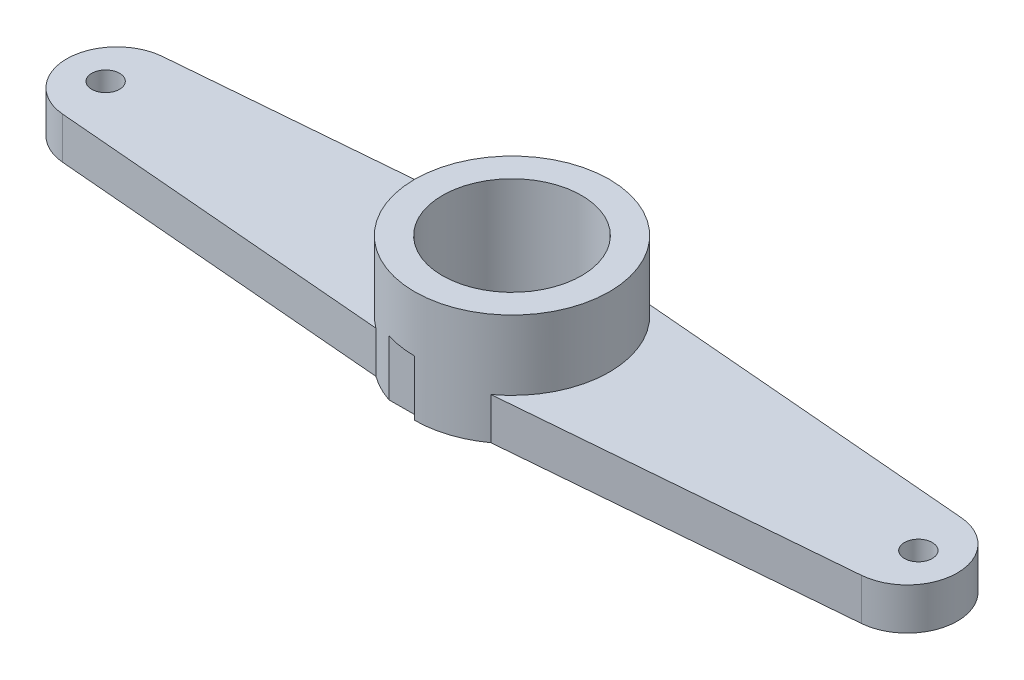
SolidWorks part; units mm, degrees
ref_plane "前视基准面" through (0, 0, 0) normal (0, 0, 1) x (1, 0, 0)
ref_plane "上视基准面" through (0, 0, 0) normal (0, 1, 0) x (1, 0, 0)
ref_plane "右视基准面" through (0, 0, 0) normal (1, 0, 0) x (0, 0, -1)
sketch "草图1" plane through (0, 0, 0) normal (0, 1, 0) x (1, 0, 0)
  line L0 (-14.2, 0) -> (14.2, 0) construction
  line L1 (0, 3) -> (0, -3) construction
  line L2 (14.3508, 1.7937) -> (0, 3)
  line L3 (14.3508, -1.7937) -> (0, -3)
  line L4 (-14.3508, 1.7937) -> (0, 3)
  line L5 (-14.3508, -1.7937) -> (0, -3)
  circle A0 centre (14.2, 0) radius 1.8
  circle A1 centre (-14.2, 0) radius 1.8
  circle A2 centre (0, 0) radius 3.4998
  point P4 (0, 0)
  point P12 (0, 0)
  dimension "D1" = 3.6
  dimension "D2" = 6
extrude "凸台-拉伸1" add sketch "草图1" along normal blind 1.5 contours A1 | A2 L4 A1 L5 | A2 L3 A0 L2 | A0 region at (7.6724, 0, 0) region at (14.2, 0, 0) region at (-7.6724, 0, 0) region at (-14.2, 0, 0)
extrude "凸台-拉伸2" add sketch "草图1<4>" along normal blind 4 contours L5 A2 L3 | L3 A2 L2 L4 L5 | L2 A2 L4 region at (0, 0, 0) region at (0, 0, -3.1481) region at (0, 0, 3.1481)
sketch "草图1<4>" plane through (0, 0, 0) normal (0, 1, 0) x (1, 0, 0) same geometry as "草图1"
sketch "草图2" plane through (0, 4, 0) normal (0, 1, 0) x (1, 0, 0)
  circle A0 centre (0, 0) radius 2.5
extrude "切除-拉伸1" cut sketch "草图2" against normal blind 4
sketch "草图3" plane through (0, 0, 0) normal (0, -1, 0) x (1, 0, 0)
  line L0 (-16, 0) -> (16, 0) construction
  line L4 (-14.3508, -1.7937) -> (-2.0637, -2.8265)
  line L5 (2.0637, -2.8265) -> (14.3508, -1.7937)
  line L6 (14.3508, 1.7937) -> (2.0637, 2.8265)
  line L7 (-2.0637, 2.8265) -> (-14.3508, 1.7937)
  line L8 (-14.3508, -1.7937) -> (-2.0637, -2.8265)
  line L9 (2.0637, -2.8265) -> (14.3508, -1.7937)
  line L10 (14.3508, 1.7937) -> (2.0637, 2.8265)
  line L11 (-2.0637, 2.8265) -> (-14.3508, 1.7937)
  circle A0 centre (14.6, 0) radius 0.5
  circle A1 centre (-14.6, 0) radius 0.5
  arc A4 (-14.3508, 1.7937) -> (-14.3508, -1.7937) centre (-14.2, 0) ccw
  arc A5 (-2.0637, -2.8265) -> (2.0637, -2.8265) centre (0, 0) ccw
  arc A6 (14.3508, -1.7937) -> (14.3508, 1.7937) centre (14.2, 0) ccw
  arc A7 (2.0637, 2.8265) -> (-2.0637, 2.8265) centre (0, 0) ccw
  arc A8 (-14.3508, 1.7937) -> (-14.3508, -1.7937) centre (-14.2, 0) ccw
  arc A9 (-2.0637, -2.8265) -> (2.0637, -2.8265) centre (0, 0) ccw
  arc A10 (14.3508, -1.7937) -> (14.3508, 1.7937) centre (14.2, 0) ccw
  arc A11 (2.0637, 2.8265) -> (-2.0637, 2.8265) centre (0, 0) ccw
  point P19 (0, 0)
  dimension "D2" = 1.4
  dimension "D3" = 1.4
  dimension "D1" = 0
extrude "切除-拉伸2" cut sketch "草图3" against normal blind 4 contours A0 | A1
sketch "草图4" plane through (0, 0, 0) normal (0, -1, 0) x (1, 0, 0)
  line L0 (0, -3.4998) -> (0, 3.4998) construction
  line L1 (1.0901, 3.3094) -> (-1.0901, 3.3256)
  line L4 (-14.3508, -1.7937) -> (-2.0637, -2.8265)
  line L5 (2.0637, -2.8265) -> (14.3508, -1.7937)
  line L6 (14.3508, 1.7937) -> (2.0637, 2.8265)
  line L7 (-2.0637, 2.8265) -> (-14.3508, 1.7937)
  line L8 (-14.3508, -1.7937) -> (-2.0637, -2.8265)
  line L9 (2.0637, -2.8265) -> (14.3508, -1.7937)
  line L10 (14.3508, 1.7937) -> (2.0637, 2.8265)
  line L11 (-2.0637, 2.8265) -> (-14.3508, 1.7937)
  arc A4 (-14.3508, 1.7937) -> (-14.3508, -1.7937) centre (-14.2, 0) ccw
  arc A5 (-2.0637, -2.8265) -> (2.0637, -2.8265) centre (0, 0) ccw
  arc A6 (14.3508, -1.7937) -> (14.3508, 1.7937) centre (14.2, 0) ccw
  arc A7 (2.0637, 2.8265) -> (-2.0637, 2.8265) centre (0, 0) ccw
  arc A8 (-14.3508, 1.7937) -> (-14.3508, -1.7937) centre (-14.2, 0) ccw
  arc A9 (-2.0637, -2.8265) -> (2.0637, -2.8265) centre (0, 0) ccw
  arc A10 (14.3508, -1.7937) -> (14.3508, 1.7937) centre (14.2, 0) ccw
  arc A11 (2.0637, 2.8265) -> (-2.0637, 2.8265) centre (0, 0) ccw
  point P10 (0, 0)
  point P18 (0, 3.3175)
  dimension "D1" = 0
extrude "切除-拉伸3" cut sketch "草图4" against normal blind 2 contours L1 L0 A11 region at (-0.4086, 0, 3.393)
sketch "草图5" plane through (0, 0, 0) normal (0, -1, 0) x (1, 0, 0)
  line L1 (-1, -1) -> (1, -1)
  line L2 (-1, -1) -> (-1, 1)
  line L3 (-1, 1) -> (1, 1)
  line L4 (1, -1) -> (1, 1)
  line L5 (-1, -1) -> (1, 1) construction
  line L6 (0, 3.3175) -> (-1.0901, 3.3256)
  line L7 (-2.0637, 2.8265) -> (-14.3508, 1.7937)
  line L8 (-14.3508, -1.7937) -> (-2.0637, -2.8265)
  line L9 (2.0637, -2.8265) -> (14.3508, -1.7937)
  line L10 (14.3508, 1.7937) -> (2.0637, 2.8265)
  line L11 (0, 3.4998) -> (0, 3.3175)
  line L12 (0, 3.3175) -> (-1.0901, 3.3256)
  line L13 (-2.0637, 2.8265) -> (-14.3508, 1.7937)
  line L14 (-14.3508, -1.7937) -> (-2.0637, -2.8265)
  line L15 (2.0637, -2.8265) -> (14.3508, -1.7937)
  line L16 (14.3508, 1.7937) -> (2.0637, 2.8265)
  line L17 (0, 3.4998) -> (0, 3.3175)
  line L18 (-1, 1) -> (1, -1) construction
  arc A5 (-1.0901, 3.3256) -> (-2.0637, 2.8265) centre (0, 0) ccw
  arc A6 (-14.3508, 1.7937) -> (-14.3508, -1.7937) centre (-14.2, 0) ccw
  arc A7 (-2.0637, -2.8265) -> (2.0637, -2.8265) centre (0, 0) ccw
  arc A8 (14.3508, -1.7937) -> (14.3508, 1.7937) centre (14.2, 0) ccw
  arc A9 (2.0637, 2.8265) -> (0, 3.4998) centre (0, 0) ccw
  arc A10 (-1.0901, 3.3256) -> (-2.0637, 2.8265) centre (0, 0) ccw
  arc A11 (-14.3508, 1.7937) -> (-14.3508, -1.7937) centre (-14.2, 0) ccw
  arc A12 (-2.0637, -2.8265) -> (2.0637, -2.8265) centre (0, 0) ccw
  arc A13 (14.3508, -1.7937) -> (14.3508, 1.7937) centre (14.2, 0) ccw
  arc A14 (2.0637, 2.8265) -> (0, 3.4998) centre (0, 0) ccw
  dimension "D2" = 2
  dimension "D3" = 2
  dimension "D1" = 0
extrude "凸台-拉伸3" add sketch "草图5" along normal blind 1 separate body contours L2 L1 L4 L3
